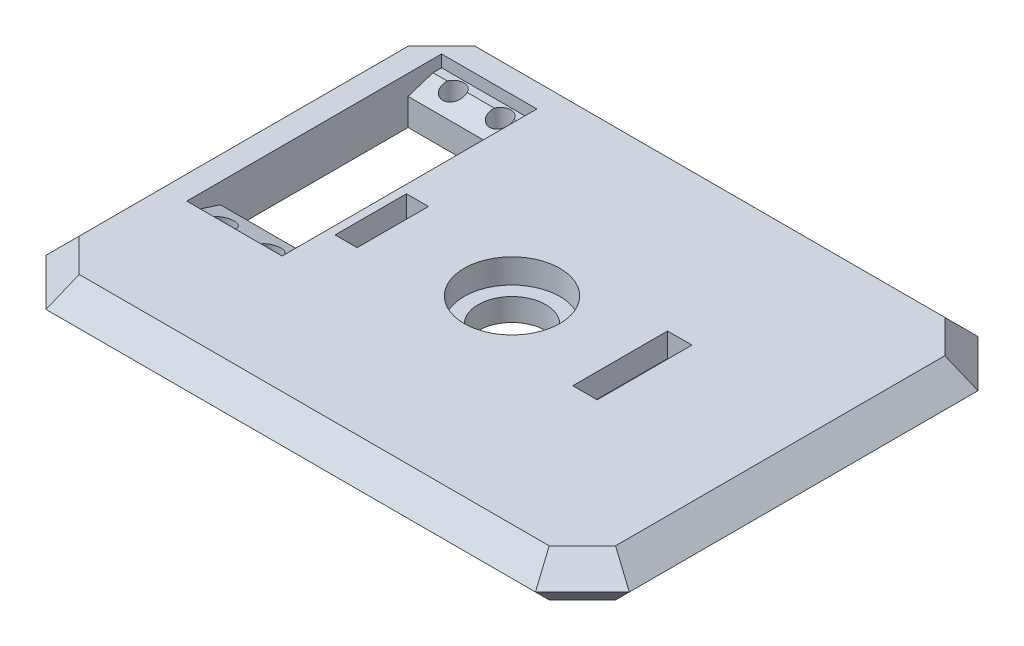
SolidWorks part; units mm, degrees
ref_plane "Front Plane" through (0, 0, 0) normal (0, 0, 1) x (1, 0, 0)
ref_plane "Top Plane" through (0, 0, 0) normal (0, 1, 0) x (1, 0, 0)
ref_plane "Right Plane" through (0, 0, 0) normal (1, 0, 0) x (0, 0, -1)
sketch "Base" plane through (0, 0, 0) normal (0, 1, 0) x (1, 0, 0)
  circle A0 centre (0, 0) radius 100
  dimension "D1" = 200
sketch "Cutout" plane through (0, 0, 0) normal (0, 1, 0) x (1, 0, 0)
  line L1 (23.15, 10) -> (28.15, 10)
  line L2 (23.15, 10) -> (23.15, -10)
  line L3 (23.15, -10) -> (28.15, -10)
  line L4 (28.15, 10) -> (28.15, -10)
  line L5 (23.15, 10) -> (28.15, -10) construction
  line L6 (23.15, -10) -> (28.15, 10) construction
  line L7 (-30, 7.5) -> (-25.5, 7.5)
  line L8 (-30, 7.5) -> (-30, -7.5)
  line L9 (-30, -7.5) -> (-25.5, -7.5)
  line L10 (-25.5, 7.5) -> (-25.5, -7.5)
  line L11 (-30, 7.5) -> (-25.5, -7.5) construction
  line L12 (-30, -7.5) -> (-25.5, 7.5) construction
  line L13 (-31.9608, 55.0093) -> (27.2905, 55.0093)
  line L14 (-31.9608, 55.0093) -> (-31.9608, 48.2128)
  line L15 (-31.9608, 48.2128) -> (27.2905, 48.2128)
  line L16 (27.2905, 55.0093) -> (27.2905, 48.2128)
  line L17 (-31.9608, 55.0093) -> (27.2905, 48.2128) construction
  line L18 (-31.9608, 48.2128) -> (27.2905, 55.0093) construction
  line L19 (23.15, 10) -> (27.75, 10)
  line L20 (23.15, 10) -> (23.15, -10)
  line L21 (23.15, -10) -> (27.75, -10)
  line L22 (27.75, 10) -> (27.75, -10)
  line L23 (-52, 30) -> (-32, 30)
  line L24 (-52, 30) -> (-52, -10)
  line L25 (-52, -10) -> (-32, -10)
  line L26 (-32, 30) -> (-32, -10)
  line L27 (-52, 30) -> (-32, -10) construction
  line L28 (-52, -10) -> (-32, 30) construction
  point P0 (25.65, 0)
  point P5 (-27.75, 0)
  point P10 (-2.3352, 51.6111)
  point P18 (-42, 10)
  point P30 (-42, 0)
  dimension "D2" = 4.6
  dimension "D3" = 5
  dimension "D4" = 20
  dimension "D5" = 20
  dimension "D6" = 40
  dimension "D7" = 10
  dimension "D8" = 27.75
  dimension "D9" = 4.5
  dimension "D10" = 15
  dimension "D11" = 27.75
  dimension "D12" = 42
extrude "Base Circle" add sketch "Base" along normal blind 10
extrude "Vert Support" cut sketch "Cutout" along normal through all from offset 5 contours L22 L1 L2 L3 | L1 L22 L3 L4 | L10 L7 L8 L9 region at (25.45, 0, 0) region at (27.95, 0, 0) region at (-27.75, 0, 0)
other ".1 Offset for vert support" flip direction yes face at (25.65, 5, 0) face at (-27.75, 5, 0) face at (25.65, 7.5, -10) face at (23.15, 7.5, 0) face at (25.65, 7.5, 10) face at (28.15, 7.5, 0) face at (-27.75, 7.5, 7.5) face at (-25.5, 7.5, 0) face at (-27.75, 7.5, -7.5) face at (-30, 7.5, 0) offset 0.1 parameters "D1"=0.1
extrude "Servo cutout" cut sketch "Cutout<3>" along normal through all contours L26 L23 L24 L25 region at (-42, 0, -10)
sketch "Cutout<3>" plane through (0, 0, 0) normal (0, 1, 0) x (1, 0, 0) same geometry as "Cutout"
sketch "Sketch4" plane through (0, 10, 0) normal (0, -1, 0) x (1, 0, 0)
  line L0 (-52, -30) -> (-32, 10) construction
  line L1 (-52, 17) -> (-32, 17)
  line L2 (-52, 17) -> (-52, -37)
  line L3 (-52, -37) -> (-32, -37)
  line L4 (-32, 17) -> (-32, -37)
  line L5 (-52, 17) -> (-32, -37) construction
  line L6 (-52, -37) -> (-32, 17) construction
  point P0 (-42, -10)
  point P2 (-42, -10)
  dimension "D1" = 54
extrude "Servo rest" cut sketch "Sketch4" along normal blind 2.4
chamfer "Servo Slant 1" distance 5.3 distance2 1.7 1 edges at (-42, 7.6, -30) first distance on face at (-42, 7.6, -33.5)
chamfer "Servo Slant 2" distance 1.7 distance2 5.3 1 edges at (-42, 7.6, 10) first distance on face at (-42, 3.8, 10)
other ".15 Servo Print Offset" flip direction yes face at (-42, 8.8, 17) face at (-42, 7.6, 16.15) face at (-42, 6.75, 12.65) face at (-32, 6.22, -10) face at (-52, 6.22, -10) face at (-42, 8.8, -37) face at (-42, 7.6, -36.15) face at (-42, 6.75, -32.65) offset 0.15 parameters "D1"=0.15
sketch "Sketch6" plane through (0, 0, 0) normal (0, -1, 0) x (1, 0, 0)
  line L0 (-52.15, -30) -> (-31.85, -30) construction
  line L1 (-47, -34.5) -> (-37, -34.5)
  line L2 (-52.15, 10) -> (-31.85, 10) construction
  circle A0 centre (-47, -34.5) radius 2.25
  circle A1 centre (-37, -34.5) radius 2.25
  circle A2 centre (-37, 14.5) radius 2.25
  circle A3 centre (-47, 14.5) radius 2.25
  circle A4 centre (-47, -34.5) radius 3.75
  circle A5 centre (-37, -34.5) radius 3.75
  circle A6 centre (-37, 14.5) radius 3.75
  circle A7 centre (-47, 14.5) radius 3.75
  point P2 (-42, 10)
  point P11 (-42, -34.5)
  point P15 (-42, -30)
  dimension "D3" = 4.5
  dimension "D5" = 7.5
  dimension "D1" = 10
  dimension "D2" = 4.5
  dimension "D4" = 4.5
extrude "M4 Thread Clearance + wiggle room" cut sketch "Sketch6" against normal through all contours A0 | A1 | A2 | A3 region at (-37, 0, -32.3136) region at (-49.1864, 0, -34.5) region at (-37, 0, 14.5) region at (-47, 0, 14.5)
extrude "M4 Socket Head Clearance + wiggle room" cut sketch "Sketch6<3>" against normal blind 2 contours A7 A3 | A6 A2 | A4 A0 | A5 A1 region at (-50.6439, 0, -34.5) region at (-37, 0, -30.8561) region at (-40.6439, 0, 14.5) region at (-50.6439, 0, 14.5)
sketch "Sketch6<3>" plane through (0, 0, 0) normal (0, -1, 0) x (1, 0, 0) same geometry as "Sketch6"
sketch "Sketch5" plane through (0, 10, 0) normal (0, 1, 0) x (1, 0, 0)
  circle A0 centre (0, 0) radius 10
  circle A1 centre (0, 0) radius 7
  point P0 (0, 0)
  point P7 (0, 0)
  dimension "D1" = 20
  dimension "D2" = 14
extrude "Central Axle Head cutout" cut sketch "Sketch5" against normal blind 5 contours A0 A1
extrude "Axle Body cutout" cut sketch "Sketch5<3>" against normal through all contours A1
sketch "Sketch5<3>" plane through (0, 10, 0) normal (0, 1, 0) x (1, 0, 0) same geometry as "Sketch5"
other ".15 Offset, Axle" flip direction yes face at (0, 5, 7) face at (0, 5, 7) face at (0, 5, 10) offset 0.2 parameters "D1"=0.2
sketch "Sketch8" plane through (0, 10, 0) normal (0, 1, 0) x (1, 0, 0)
  line L0 (-52.15, 37.15) -> (-52.15, -17.15) construction
  line L1 (-62.15, 47.15) -> (62.15, 47.15)
  line L2 (-62.15, 47.15) -> (-62.15, -47.15)
  line L3 (-62.15, -47.15) -> (62.15, -47.15)
  line L4 (62.15, 47.15) -> (62.15, -47.15)
  line L5 (-62.15, 47.15) -> (62.15, -47.15) construction
  line L6 (-62.15, -47.15) -> (62.15, 47.15) construction
  line L7 (-52.15, 37.15) -> (-31.85, 37.15) construction
  point P0 (0, 0)
  dimension "D1" = 10
  dimension "D2" = 10
extrude "Intersect Tool" add sketch "Sketch8" against normal blind 10 separate body
combine bodies "Intersect with tool" operation type common bodies to combine 110 114
chamfer "Corner Chamfer" distance 10 angle 45 4 edges at (62.15, 5, -47.15) (-62.15, 5, -47.15) (62.15, 5, 47.15) (-62.15, 5, 47.15)
chamfer "Edge Chamfer" distance 5 angle 45 16 edges at (-57.15, 10, -42.15) (0, 10, -47.15) (57.15, 10, -42.15) (62.15, 10, 0) (57.15, 10, 42.15) (0, 10, 47.15) (-57.15, 10, 42.15) (-62.15, 10, 0) (-57.15, 0, -42.15) (0, 0, -47.15) (57.15, 0, -42.15) (62.15, 0, 0) (57.15, 0, 42.15) (-62.15, 0, 0) (-57.15, 0, 42.15) (0, 0, 47.15)
equation "\"D3@Sketch6\"=4+ .5"
equation "\"D5@Sketch6\"=7+.5"
equation "\"D1@Sketch6\"=5.5 + 4.5"
